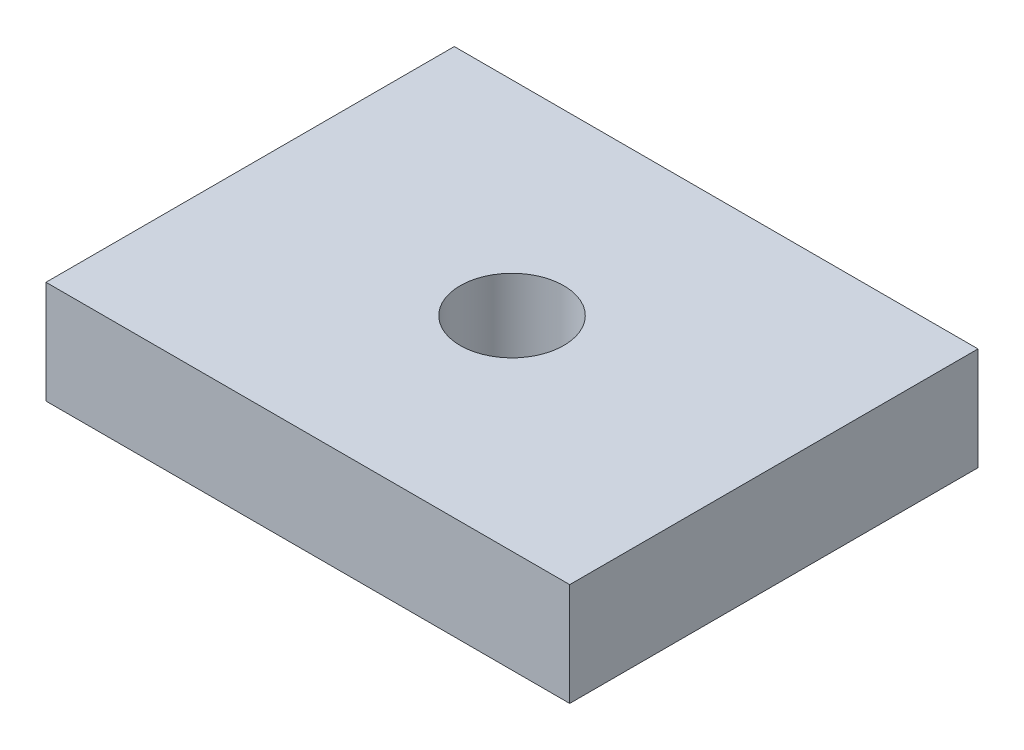
SolidWorks part; units mm, degrees
ref_plane "Front Plane" through (0, 0, 0) normal (0, 0, 1) x (1, 0, 0)
ref_plane "Top Plane" through (0, 0, 0) normal (0, 1, 0) x (1, 0, 0)
ref_plane "Right Plane" through (0, 0, 0) normal (1, 0, 0) x (0, 0, -1)
sketch "Sketch1" plane through (0, 0, 0) normal (0, 1, 0) x (1, 0, 0)
  line L1 (-25.4423, -19.8349) -> (25.4423, -19.8349)
  line L2 (-25.4423, -19.8349) -> (-25.4423, 19.8349)
  line L3 (-25.4423, 19.8349) -> (25.4423, 19.8349)
  line L4 (25.4423, -19.8349) -> (25.4423, 19.8349)
  line L5 (-25.4423, -19.8349) -> (25.4423, 19.8349) construction
  line L6 (-25.4423, 19.8349) -> (25.4423, -19.8349) construction
  point P0 (0, 0)
extrude "Boss-Extrude1" add sketch "Sketch1" along normal blind 10
sketch "Sketch2" plane through (0, 10, 0) normal (0, 1, 0) x (1, 0, 0)
  circle A0 centre (0, 0) radius 5.0366
extrude "Cut-Extrude1" cut sketch "Sketch2" against normal blind 10
